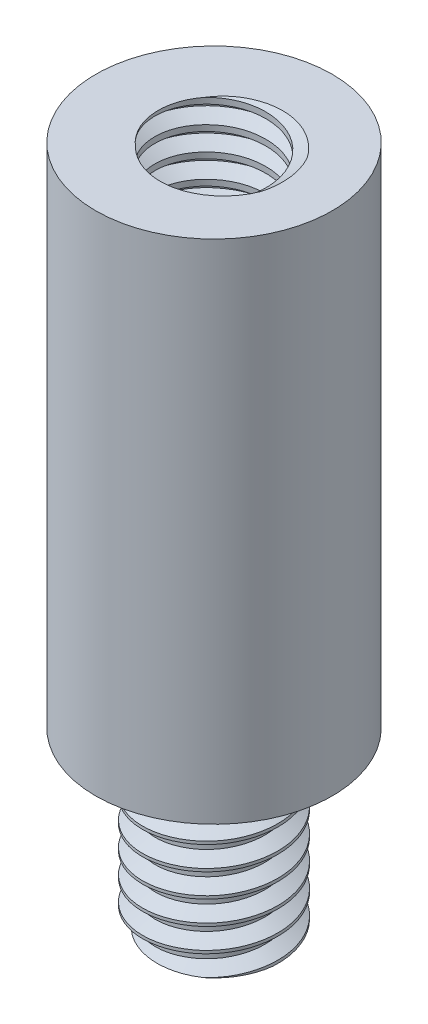
SolidWorks part; units mm, degrees
ref_plane "Front Plane" through (0, 0, 0) normal (0, 0, 1) x (1, 0, 0)
ref_plane "Top Plane" through (0, 0, 0) normal (0, 1, 0) x (1, 0, 0)
ref_plane "Right Plane" through (0, 0, 0) normal (1, 0, 0) x (0, 0, -1)
sketch "Sketch1" plane through (0, 0, 0) normal (0, 1, 0) x (1, 0, 0)
  circle A0 centre (0, 0) radius 3.5
  dimension "D1" = 7
extrude "Boss-Extrude1" add sketch "Sketch1" along normal mid plane 15
sketch "Sketch2" plane through (0, 7.5, 0) normal (0, 1, 0) x (1, 0, 0)
  circle A0 centre (0, 0) radius 1.65
  dimension "D1" = 3.3
extrude "Cut-Extrude1" cut sketch "Sketch2" against normal blind 6.5
thread "Thread1" pitch 0.7 method cut profile "Thread Profile1" start angle 0, offset 2, length 8, pitch 0.7, diameter 3.3
ref_plane "Plane1" through (-1.65, 9.5, 0) normal (0, 0, 1) x (-1, 0, 0)
sketch "Thread Profile1" plane through (-1.65, 9.5, 0) normal (0, 0, 1) x (-1, 0, 0)
  line L0 (0, 0) -> (0, 0.7) construction
  line L1 (0, 0) -> (0.3789, 0.2187)
  line L2 (0.3789, 0.2187) -> (0.3789, 0.3062)
  line L3 (0.3789, 0.3062) -> (0, 0.525)
  line L4 (0.3789, 0.2625) -> (0, 0.2625) construction
  line L11 (0, 0) -> (0, 0.525)
  point P2 (0, 0)
  dimension "Pitch" = 0.7
  dimension "Profile_Angle" = 60
  dimension "Profile_Land" = 0.0875
  dimension "Profile_Height" = 0.3789
mirror "Mirror3" [suppressed] about plane through (0, 0, 0) normal (0, 1, 0)
thread "Thread2" [suppressed] pitch 0.7 start angle 0, offset 2, length 8, pitch 0.7, diameter 3.3
ref_plane "Plane2" through (1.65, -9.5, 0) normal (0, 0, 1) x (1, 0, 0)
sketch "Thread Profile2" plane through (1.65, -9.5, 0) normal (0, 0, 1) x (1, 0, 0)
  line L0 (0, 0) -> (0, 0.7) construction
  line L1 (0, 0) -> (0.3789, 0.2187)
  line L2 (0.3789, 0.2187) -> (0.3789, 0.3062)
  line L3 (0.3789, 0.3062) -> (0, 0.525)
  line L4 (0.3789, 0.2625) -> (0, 0.2625) construction
  line L11 (0, 0) -> (0, 0.525)
  point P2 (0, 0)
  dimension "Pitch" = 0.7
  dimension "Profile_Angle" = 60
  dimension "Profile_Land" = 0.0875
  dimension "Profile_Height" = 0.3789
sketch "Sketch3" plane through (0, -7.5, 0) normal (0, -1, 0) x (1, 0, 0)
  circle A0 centre (0, 0) radius 2
  dimension "D1" = 4
extrude "Boss-Extrude2" add sketch "Sketch3" along normal blind 5
thread "Thread3" pitch 0.7 method cut profile "Thread Profile3" start angle 0, offset 2, length 7, pitch 0.7, diameter 4
ref_plane "Plane3" through (2, -14.5, 0) normal (0, 0, 1) x (1, 0, 0)
sketch "Thread Profile3" plane through (2, -14.5, 0) normal (0, 0, 1) x (1, 0, 0)
  line L0 (0, 0) -> (0, 0.7) construction
  line L11 (0, 0) -> (0, 0.6125)
  line L12 (0, 0.6125) -> (-0.3789, 0.3937)
  line L13 (-0.3789, 0.3937) -> (-0.3789, 0.2187)
  line L15 (-0.3789, 0.2187) -> (0, 0)
  line L17 (-0.3789, 0.3062) -> (0, 0.3062) construction
  point P2 (0, 0)
  dimension "Pitch" = 0.7
  dimension "Profile_Angle" = 60
  dimension "Profile_Land" = 0.175
  dimension "Profile_Height" = 0.3789
